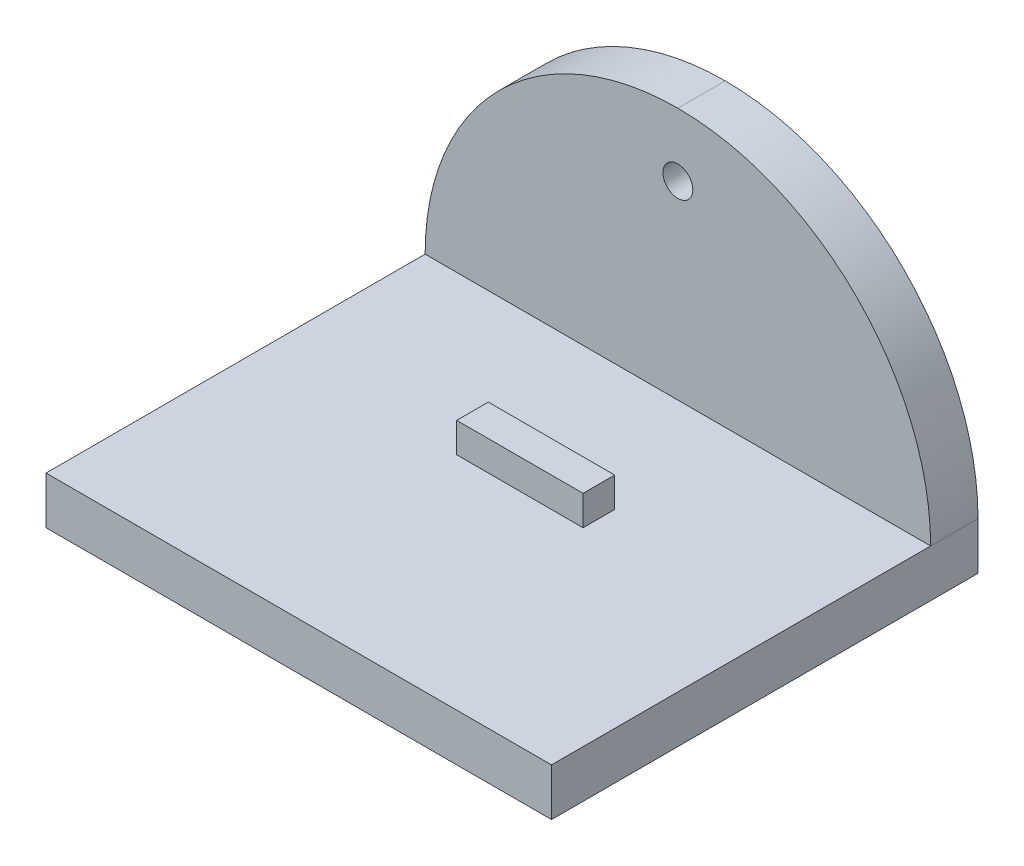
SolidWorks part; units mm, degrees
ref_plane "Front Plane" through (0, 0, 0) normal (0, 0, 1) x (1, 0, 0)
ref_plane "Top Plane" through (0, 0, 0) normal (0, 1, 0) x (1, 0, 0)
ref_plane "Right Plane" through (0, 0, 0) normal (1, 0, 0) x (0, 0, -1)
sketch "Sketch1" plane through (0, 0, 0) normal (1, 0, 0) x (0, 0, -1)
  line L0 (0, 0) -> (-42.8625, 0)
  line L1 (-42.8625, 0) -> (-42.8625, 4.7625)
  line L2 (-42.8625, 4.7625) -> (-4.7625, 4.7625)
  line L3 (-4.7625, 4.7625) -> (-4.7625, 30.1625)
  line L4 (-4.7625, 30.1625) -> (0, 30.1625)
  line L5 (0, 30.1625) -> (0, 0)
  dimension "D1" = 38.1
  dimension "D2" = 25.4
  dimension "D3" = 4.7625
extrude "Boss-Extrude1" add sketch "Sketch1" along normal blind 50.8
sketch "Sketch2" plane through (0, 4.7625, 0) normal (0, 1, 0) x (1, 0, 0)
  line L0 (50.8, -42.8625) -> (0, -42.8625) construction
  line L1 (19.05, -20.6375) -> (31.75, -20.6375)
  line L2 (19.05, -20.6375) -> (19.05, -17.4625)
  line L3 (19.05, -17.4625) -> (31.75, -17.4625)
  line L4 (31.75, -20.6375) -> (31.75, -17.4625)
  line L7 (50.8, -4.7625) -> (0, -4.7625) construction
  point P4 (25.4, -20.6375)
  point P7 (25.4, -42.8625)
  dimension "D1" = 3.175
  dimension "D2" = 12.7
  dimension "D3" = 12.7
extrude "Boss-Extrude2" add sketch "Sketch2" along normal blind 2.9972
sketch "Sketch3" plane through (0, 0, 4.7625) normal (0, 0, 1) x (1, 0, 0)
  line L0 (50.8, 30.1625) -> (0, 30.1625) construction
  line L1 (50.8, 4.7625) -> (0, 4.7625) construction
  circle A0 centre (25.4, 23.8125) radius 1.5
  point P5 (25.4, 30.1625)
  dimension "D1" = 3
  dimension "D2" = 19.05
extrude "Cut-Extrude1" cut sketch "Sketch3" against normal through all
fillet "Fillet1" radius 25.4 2 edges at (0, 30.1625, 2.3813) (50.8, 30.1625, 2.3813)
